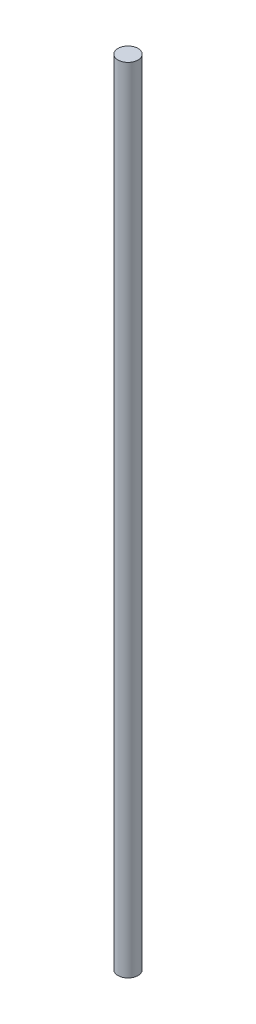
SolidWorks part; units mm, degrees
ref_plane "Front Plane" through (0, 0, 0) normal (0, 0, 1) x (1, 0, 0)
ref_plane "Top Plane" through (0, 0, 0) normal (0, 1, 0) x (1, 0, 0)
ref_plane "Right Plane" through (0, 0, 0) normal (1, 0, 0) x (0, 0, -1)
sketch "Sketch1" plane through (0, 0, 0) normal (0, 1, 0) x (1, 0, 0)
  circle A0 centre (0, 0) radius 3
  dimension "D1" = 6
extrude "Boss-Extrude1" add sketch "Sketch1" along normal blind 236.982
ref_axis "Axis1" through (0, 236.982, 0) along (0, -1, 0)
